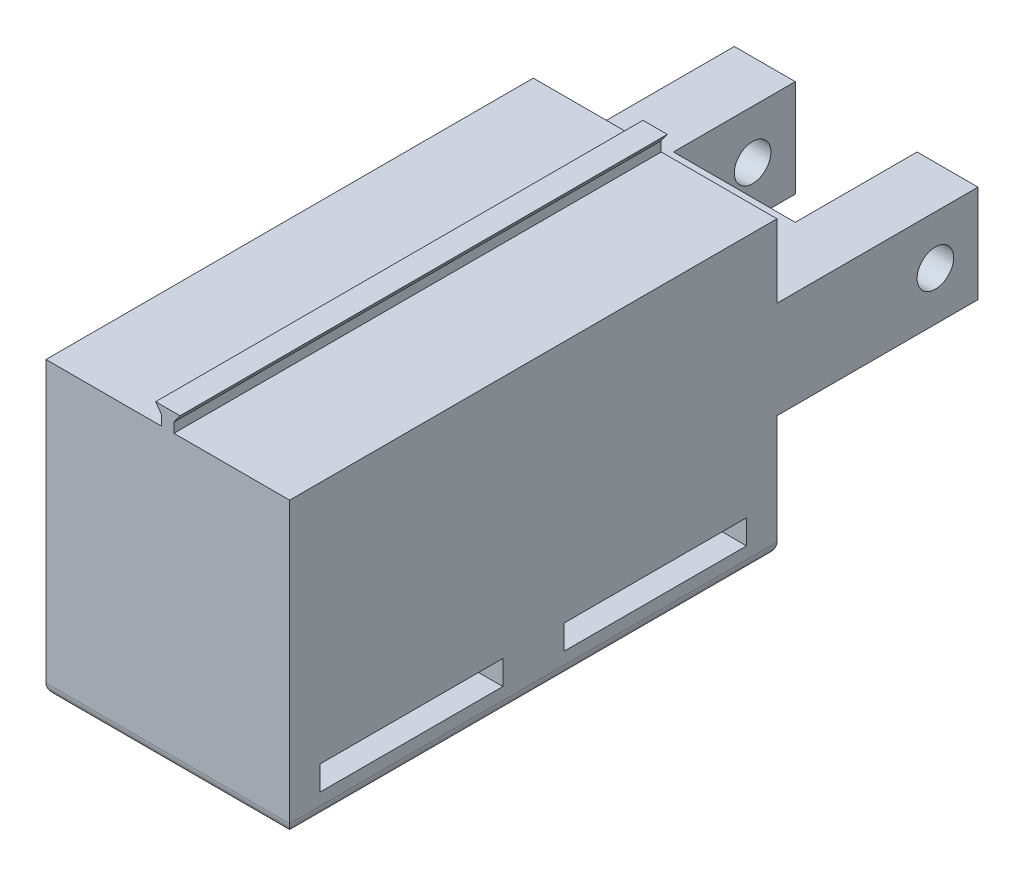
SolidWorks part; units mm, degrees
ref_plane "Alzado" through (0, 0, 0) normal (0, 0, 1) x (1, 0, 0)
ref_plane "Planta" through (0, 0, 0) normal (0, 1, 0) x (1, 0, 0)
ref_plane "Vista lateral" through (0, 0, 0) normal (1, 0, 0) x (0, 0, -1)
sketch "Croquis1" plane through (0, 0, 0) normal (1, 0, 0) x (0, 0, -1)
  line L0 (0, 9) -> (0, 1) construction
  line L9 (-1.5, 9) -> (-58, 9) construction
  line L18 (0, 9) -> (0, -9) construction
  line L19 (0, -9) -> (-58, -9) construction
  line L25 (0, 1) -> (-18, 1) construction
  line L26 (0, 1) -> (0, -2.6179) construction
  line L29 (0, -2.6179) -> (0, -9) construction
  line L31 (-1.5, 9) -> (-1.5, 1)
  line L32 (-18, 1) -> (-1.5, 1)
  line L35 (-58, -9) -> (-18, -9)
  line L56 (-58, 9) -> (-58, -9)
  line L59 (0, 9) -> (-58, 9) construction
  line L61 (-18, 1) -> (-18, -9)
  line L62 (-18, 9) -> (-18, 15)
  line L63 (-18, 15) -> (-58, 15)
  line L64 (-58, 15) -> (-58, 9)
  line L65 (-1.5, 9) -> (-18, 9)
  circle A0 centre (-5, 5) radius 1.5
  point P9 (0, 0)
  point P12 (0, 5)
  dimension "D6" = 3
  dimension "D1" = 58
  dimension "D2" = 10
  dimension "D3" = 40
  dimension "D4" = 8
  dimension "D5" = 6
  dimension "D7" = 5
  dimension "D8" = 3
extrude "Saliente-Extruir1" add sketch "Croquis1" along normal mid plane 20
sketch "Croquis2" plane through (0, 0, 0) normal (0, 1, 0) x (1, 0, 0)
  line L5 (10, -1.5) -> (-10, -1.5) construction
  line L8 (-5, -1.5) -> (5, -1.5)
  line L9 (-5, -1.5) -> (-5, -11.5)
  line L10 (-5, -11.5) -> (5, -11.5)
  line L11 (5, -1.5) -> (5, -11.5)
  point P6 (0, -1.5)
  dimension "D1" = 10
  dimension "D2" = 10
extrude "Cortar-Extruir1" cut sketch "Croquis2" against normal through all both and the other way through all
sketch "Croquis4" plane through (0, 0, 0) normal (1, 0, 0) x (0, 0, -1)
  line L0 (-58, -9) -> (-18, -9) construction
  line L1 (-55.5, -5) -> (-40.5, -5)
  line L2 (-55.5, -5) -> (-55.5, -7)
  line L3 (-55.5, -7) -> (-40.5, -7)
  line L4 (-40.5, -5) -> (-40.5, -7)
  line L5 (-55.5, -5) -> (-40.5, -7) construction
  line L6 (-55.5, -7) -> (-40.5, -5) construction
  line L7 (-18, -9) -> (-18, 1) construction
  line L8 (-35.5, -5) -> (-20.5, -5)
  line L9 (-35.5, -5) -> (-35.5, -7)
  line L10 (-35.5, -7) -> (-20.5, -7)
  line L11 (-20.5, -5) -> (-20.5, -7)
  line L12 (-58, 15) -> (-58, -9) construction
  point P0 (-48, -6)
  point P7 (-28, -7)
  point P16 (-48, -7)
  dimension "D1" = 2
  dimension "D2" = 2
  dimension "D3" = 15
  dimension "D4" = 10
  dimension "D5" = 10
extrude "Cortar-Extruir4" cut sketch "Croquis4" against normal through all both and the other way through all
fillet "Redondeo2" radius 1 4 edges at (10, -9, 38) (-10, -9, 38) (0, -9, 58) (0, -9, 18)
sketch "Croquis5" plane through (0, 0, 18) normal (0, 0, -1) x (-1, 0, 0)
  line L0 (-10, 15) -> (10, 15) construction
  line L1 (-0.5, 15) -> (0.5, 15)
  line L2 (-0.5, 15) -> (-0.5, 15.8)
  line L4 (0.5, 15) -> (0.5, 15.8)
  line L5 (-0.5, 15.8) -> (-1, 16.5)
  line L6 (-1, 16.5) -> (1, 16.5)
  line L7 (1, 16.5) -> (0.5, 15.8)
  point P6 (0, 15)
  point P8 (0, 16.5)
  dimension "D1" = 1
  dimension "D2" = 1.5
  dimension "D3" = 0.8
  dimension "D4" = 2
extrude "Saliente-Extruir2" add sketch "Croquis5" against normal up to surface (40 mm away) up to face at (0, 3.5, 58)
